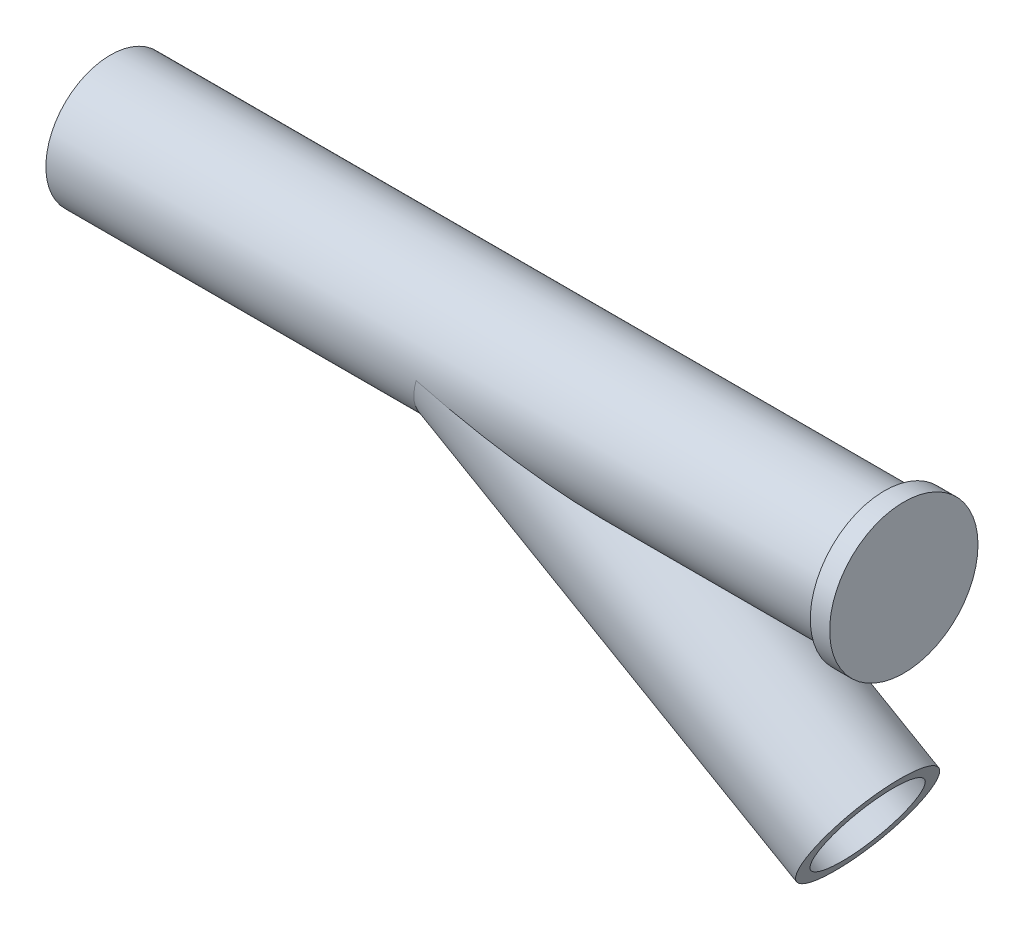
SolidWorks part; units mm, degrees
ref_plane "Front Plane" through (0, 0, 0) normal (0, 0, 1) x (1, 0, 0)
ref_plane "Top Plane" through (0, 0, 0) normal (0, 1, 0) x (1, 0, 0)
ref_plane "Right Plane" through (0, 0, 0) normal (1, 0, 0) x (0, 0, -1)
sketch "Sketch3" plane through (0, 0, 0) normal (0, 0, 1) x (1, 0, 0)
  line L0 (-57.3912, 0) -> (62.6088, 0)
  line L2 (0, 0) -> (60, -34.641)
  dimension "D1" = 120
  dimension "D2" = 30
  dimension "D3" = 60
sweep "Sweep1" add path "Sketch3" circular profile diameter 20 parameters "D3"=20
sweep "Sweep2" add path "Sketch3<4>" circular profile diameter 20 parameters "D3"=20
sketch "Sketch3<4>" plane through (0, 0, 0) normal (0, 0, 1) x (1, 0, 0) same geometry as "Sketch3"
shell "Shell2" thickness 2 removed face at (-57.3912, 0, -10) removed face at (65, -25.9808, 0) removed face at (62.6088, 0, -10)
sketch "Sketch27" plane through (62.6088, 0, 0) normal (1, 0, 0) x (0, 0, -1)
  circle A0 centre (0, 0) radius 11.5
  dimension "D1" = 23
extrude "Boss-Extrude2" add sketch "Sketch27" along normal blind 3
scale "Scale1" scale about origin uniform scaling yes scale factor 0.1
